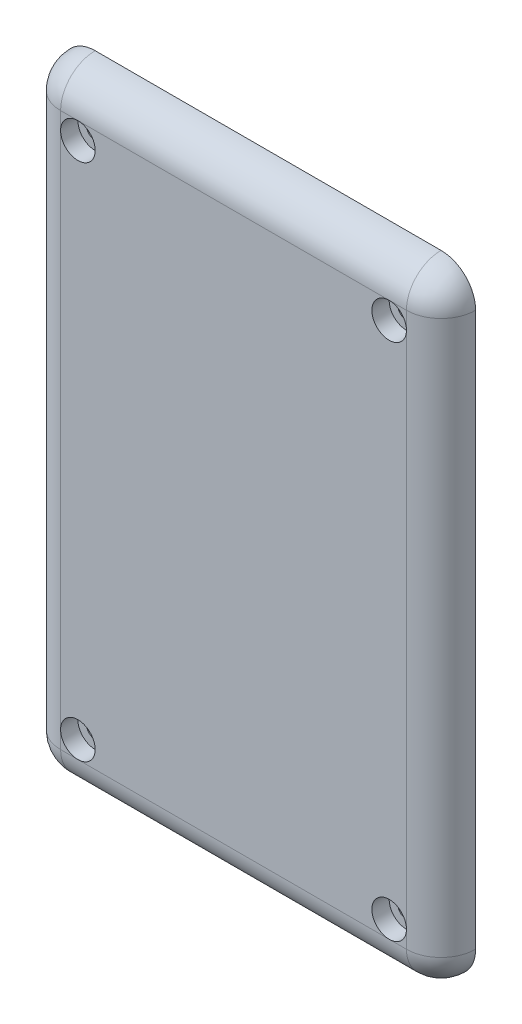
SolidWorks part; units mm, degrees
other "标注1"
sketch "草图6" plane through (-121.7901, 77.7286, -9) normal (-0.0529, 0.1135, -0.9921) x (-0.9984, 0.0112, 0.0545)
ref_plane "前视基准面" through (0, 0, 0) normal (0, 0, 1) x (1, 0, 0)
ref_plane "上视基准面" through (0, 0, 0) normal (0, 1, 0) x (1, 0, 0)
ref_plane "右视基准面" through (0, 0, 0) normal (1, 0, 0) x (0, 0, -1)
sketch "草图1" plane through (0, 0, 0) normal (0, 0, 1) x (1, 0, 0)
  line L1 (-97.7901, 77.7286) -> (-121.7901, 77.7286)
  line L2 (-97.7901, 77.7286) -> (-97.7901, 41.7286)
  line L3 (-97.7901, 41.7286) -> (-121.7901, 41.7286)
  line L4 (-121.7901, 77.7286) -> (-121.7901, 41.7286)
  dimension "D1" = 24
  dimension "D2" = 36
extrude "凸台-拉伸1" add sketch "草图1" along normal blind 2
fillet "圆角1" radius 2 4 edges at (-121.7901, 59.7286, 2) (-109.7901, 41.7286, 2) (-97.7901, 59.7286, 2) (-109.7901, 77.7286, 2)
sketch "草图4" plane through (0, 0, 0) normal (0, 0, -1) x (-1, 0, 0)
  line L0 (99.7901, 77.7286) -> (119.7901, 77.7286) construction
  line L2 (121.7901, 75.7286) -> (121.7901, 43.7286) construction
  circle A0 centre (117.9501, 65.9786) radius 2.05
  dimension "D1" = 11.75
  dimension "D3" = 4.1
  dimension "D2" = 3.84
extrude "切除-拉伸1" cut sketch "草图4" against normal blind 1
sketch "草图9" plane through (0, 0, 2) normal (0, 0, 1) x (1, 0, 0)
  line L0 (-97.7901, 43.7286) -> (-97.7901, 75.7286) construction
  line L2 (-119.7901, 41.7286) -> (-99.7901, 41.7286) construction
  line L3 (-99.7901, 77.7286) -> (-119.7901, 77.7286) construction
  line L4 (-121.7901, 75.7286) -> (-121.7901, 43.7286) construction
  circle A0 centre (-100.7901, 74.7286) radius 1
  circle A1 centre (-100.7901, 44.7286) radius 1
  circle A2 centre (-118.7901, 44.7286) radius 1
  circle A3 centre (-118.7901, 74.7286) radius 1
  dimension "D1" = 3
  dimension "D2" = 3
  dimension "D3" = 3
  dimension "D4" = 3
extrude "切除-拉伸3" cut sketch "草图9" against normal blind 1
sketch "草图10" plane through (0, 0, 1) normal (0, 0, 1) x (1, 0, 0)
  circle A0 centre (-118.7901, 44.7286) radius 0.5
  circle A1 centre (-100.7901, 44.7286) radius 0.5
  circle A2 centre (-100.7901, 74.7286) radius 0.5
  circle A3 centre (-118.7901, 74.7286) radius 0.5
  circle A5 centre (-118.7901, 74.7286) radius 1 construction
  circle A6 centre (-100.7901, 74.7286) radius 1 construction
  circle A7 centre (-118.7901, 44.7286) radius 1 construction
  circle A8 centre (-100.7901, 44.7286) radius 1 construction
  dimension "D1" = 1
extrude "切除-拉伸4" cut sketch "草图10" against normal up to next
